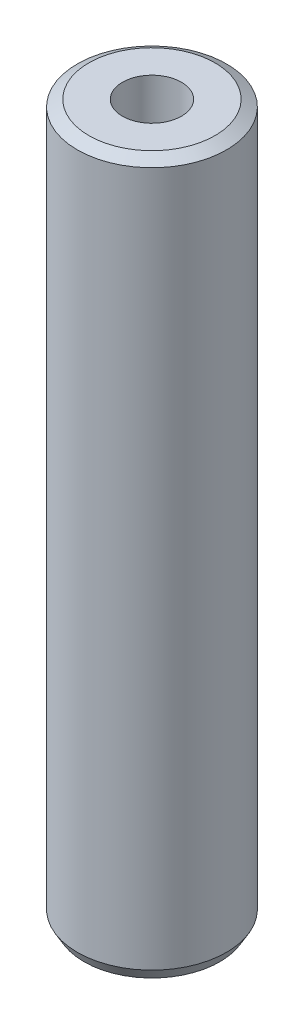
SolidWorks part; units mm, degrees
ref_plane "Front Plane" through (0, 0, 0) normal (0, 0, 1) x (1, 0, 0)
ref_plane "Top Plane" through (0, 0, 0) normal (0, 1, 0) x (1, 0, 0)
ref_plane "Right Plane" through (0, 0, 0) normal (1, 0, 0) x (0, 0, -1)
sketch "Sketch1" plane through (0, 0, 0) normal (0, 1, 0) x (1, 0, 0)
  circle A0 centre (0, 0) radius 50
  dimension "SHAFT_OD" = 100
extrude "Boss-Extrude1" add sketch "Sketch1" along normal blind 478.1317
sketch "Sketch2" plane through (0, 0, 0) normal (0, 1, 0) x (1, 0, 0)
  circle A0 centre (0, 0) radius 19.7748
  dimension "BORE_D" = 39.5497
extrude "Cut-Extrude1" cut sketch "Sketch2" along normal through all
chamfer "Chamfer1" distance 4.4479 angle 60 2 edges at (0, 478.1317, 50) (0, 0, 50) first distance on face at (0, 478.1317, 50) first distance on face at (0, 0, 19.7748)
